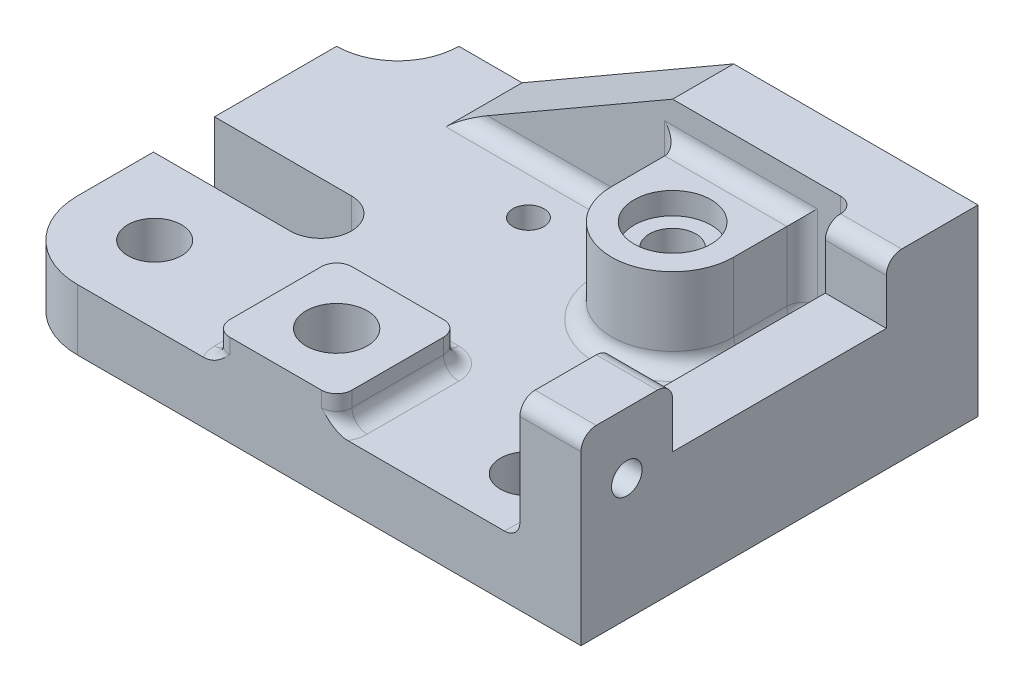
SolidWorks part; units mm, degrees
ref_plane "Front Plane" through (0, 0, 0) normal (0, 0, 1) x (1, 0, 0)
ref_plane "Top Plane" through (0, 0, 0) normal (0, 1, 0) x (1, 0, 0)
ref_plane "Right Plane" through (0, 0, 0) normal (1, 0, 0) x (0, 0, -1)
sketch "Sketch1" plane through (0, 0, 0) normal (0, 1, 0) x (1, 0, 0)
  line L1 (-60.325, 41.275) -> (60.325, 41.275)
  line L2 (-60.325, 41.275) -> (-60.325, -41.275)
  line L3 (-60.325, -41.275) -> (60.325, -41.275)
  line L4 (60.325, 41.275) -> (60.325, -41.275)
  line L5 (-60.325, 41.275) -> (60.325, -41.275) construction
  line L6 (-60.325, -41.275) -> (60.325, 41.275) construction
  point P0 (0, 0)
  dimension "D1" = 82.55
  dimension "D2" = 120.65
extrude "Boss-Extrude1" add sketch "Sketch1" along normal blind 12.7
ref_plane "Plane1" through (0, 12.7, 0) normal (0, 1, 0) x (1, 0, 0)
sketch "Sketch2" plane through (0, 12.7, 0) normal (0, 1, 0) x (1, 0, 0)
  line L0 (60.325, 41.275) -> (-60.325, 41.275) construction
  line L1 (-60.325, 41.275) -> (-60.325, -41.275) construction
  line L2 (-47.625, 41.275) -> (-60.325, 41.275)
  line L3 (-60.325, 41.275) -> (-60.325, 28.575)
  line L4 (-60.325, 3.175) -> (-31.877, 3.175)
  line L6 (-31.877, -9.525) -> (-60.325, -9.525)
  line L7 (-60.325, -9.525) -> (-60.325, 3.175)
  line L8 (9.525, 41.275) -> (9.525, 28.575)
  line L9 (9.525, 28.575) -> (47.625, 28.575)
  line L10 (47.625, 28.575) -> (47.625, -41.275)
  line L11 (-60.325, -41.275) -> (60.325, -41.275) construction
  line L12 (47.625, -41.275) -> (60.325, -41.275)
  line L13 (60.325, -41.275) -> (60.325, 41.275)
  line L14 (60.325, 41.275) -> (9.525, 41.275)
  line L18 (36.449, 28.575) -> (11.049, 28.575)
  line L19 (36.449, 28.575) -> (11.049, 28.575)
  line L20 (-15.875, -41.275) -> (-15.875, -15.875)
  line L21 (-15.875, -15.875) -> (9.525, -15.875)
  line L22 (9.525, -15.875) -> (9.525, -41.275)
  line L23 (9.525, -41.275) -> (-15.875, -41.275)
  line L24 (36.449, -9.525) -> (36.449, -28.575) construction
  line L25 (36.449, -28.575) -> (36.449, -41.275) construction
  line L26 (11.049, 28.575) -> (11.049, 14.351)
  line L28 (36.449, 14.351) -> (36.449, 28.575)
  line L29 (36.449, 28.575) -> (11.049, 28.575)
  line L30 (23.749, 28.575) -> (23.749, 1.651) construction
  line L31 (11.049, 14.351) -> (36.449, 14.351) construction
  arc A0 (-47.625, 41.275) -> (-60.325, 28.575) centre (-60.325, 41.275) cw
  arc A1 (-31.877, 3.175) -> (-31.877, -9.525) centre (-31.877, -3.175) cw
  circle A3 centre (36.449, -9.525) radius 5.588
  circle A4 centre (36.449, -28.575) radius 5.588
  circle A5 centre (-9.525, 17.653) radius 3.2312
  circle A6 centre (-44.323, -25.273) radius 5.588
  circle A7 centre (-3.175, -28.575) radius 6.35
  arc A8 (11.049, 14.351) -> (36.449, 14.351) centre (23.749, 14.351) ccw
  dimension "D1" = 12.7
  dimension "D3" = 6.35
  dimension "D7" = 11.176
  dimension "D8" = 11.176
  dimension "D9" = 11.176
  dimension "D14" = 14.224
  dimension "D26" = 12.7
  dimension "D13" = 12.7
  dimension "D2" = 28.448
  dimension "D4" = 38.1
  dimension "D5" = 16.002
  dimension "D6" = 16.002
  dimension "D10" = 19.05
  dimension "D11" = 12.7
  dimension "D12" = 11.176
  dimension "D15" = 12.7
  dimension "D16" = 12.7
  dimension "D17" = 12.7
  dimension "D18" = 50.8
  dimension "D19" = 23.622
  dimension "D20" = 50.8
  dimension "D21" = 50.8
  dimension "D22" = 25.4
  dimension "D23" = 25.4
  dimension "D24" = 12.7
  dimension "D25" = 12.7
fillet "Fillet1" radius 16.002 1 edges at (-60.325, 6.35, 41.275)
extrude "Cut-Extrude1" cut sketch "Sketch2" against normal blind 12.7 contours A1 L6 L7 L4 | A0 L3 L2 | A5 | A6 | A3 | A4 | A7
extrude "Boss-Extrude2" add sketch "Sketch2<5>" along normal blind 6.35 contours L22 L23 L20 L21 | A7
sketch "Sketch2<5>" plane through (0, 12.7, 0) normal (0, 1, 0) x (1, 0, 0) same geometry as "Sketch2"
extrude "Boss-Extrude3" add sketch "Sketch2<6>" along normal blind 25.4 contours L13 L14 L8 L9 L10 L12 region at (34.925, 12.7, -40.3057)
sketch "Sketch2<6>" plane through (0, 12.7, 0) normal (0, 1, 0) x (1, 0, 0) same geometry as "Sketch2"
extrude "Boss-Extrude4" add sketch "Sketch2<10>" along normal blind 17.526 contours L26 A8 L28 L29
sketch "Sketch2<10>" plane through (0, 12.7, 0) normal (0, 1, 0) x (1, 0, 0) same geometry as "Sketch2"
ref_plane "Plane4" through (0, 0, -41.275) normal (0, 0, -1) x (-1, 0, 0)
sketch "Sketch4" plane through (0, 0, -41.275) normal (0, 0, -1) x (-1, 0, 0)
  line L0 (-9.525, 38.1) -> (-9.525, 12.7)
  line L1 (-9.525, 12.7) -> (34.4691, 12.7)
  line L2 (-9.525, 12.7) -> (47.625, 12.7) construction
  line L3 (34.4691, 12.7) -> (-9.525, 38.1)
  dimension "D1" = 30
extrude "Boss-Extrude5" add sketch "Sketch4" against normal blind 12.7
fillet "Fillet2" radius 3.175 10 edges at (36.449, 12.7, -21.463) (23.749, 12.7, -1.651) (47.625, 25.4, -28.575) (36.449, 21.463, -28.575) (23.749, 30.226, -28.575) (11.049, 21.463, -28.575) (47.625, 12.7, 6.35) (42.037, 12.7, -28.575) (11.049, 12.7, -21.463) (-11.71, 12.7, -28.575)
fillet "Fillet3" radius 3.175 4 edges at (9.525, 15.875, 41.275) (9.525, 15.875, 15.875) (-15.875, 15.875, 15.875) (-15.875, 15.875, 41.275)
fillet "Fillet4" radius 3.175 7 edges at (-14.9451, 12.7, 40.3451) (8.5951, 12.7, 40.3451) (9.525, 12.7, 28.575) (8.5951, 12.7, 16.8049) (-3.175, 12.7, 15.875) (-14.9451, 12.7, 16.8049) (-15.875, 12.7, 28.575)
ref_plane "Plane5" through (0, 30.226, 0) normal (0, 1, 0) x (1, 0, 0)
sketch "Sketch5" plane through (0, 30.226, 0) normal (0, 1, 0) x (1, 0, 0)
  line L0 (23.749, 1.651) -> (23.749, 28.575) construction
  line L1 (7.874, 28.575) -> (39.624, 28.575) construction
  arc A0 (11.049, 14.351) -> (36.449, 14.351) centre (23.749, 14.351) ccw construction
  circle A2 centre (23.749, 14.351) radius 8.001
  point P9 (0, 0)
  dimension "D2" = 16.002
  dimension "D1" = 14.224
extrude "Cut-Extrude2" cut sketch "Sketch5" against normal blind 4.572 contours A2
ref_plane "Plane6" through (0, 25.654, 0) normal (0, 1, 0) x (1, 0, 0)
sketch "Sketch6" plane through (0, 25.654, 0) normal (0, 1, 0) x (1, 0, 0)
  circle A0 centre (23.749, 14.351) radius 4.826
  dimension "D1" = 9.652
extrude "Cut-Extrude3" cut sketch "Sketch6" against normal blind 25.654
ref_plane "Plane7" through (60.325, 0, 0) normal (1, 0, 0) x (0, 0, -1)
sketch "Sketch7" plane through (60.325, 0, 0) normal (1, 0, 0) x (0, 0, -1)
  line L0 (-22.225, 38.1) -> (-22.225, 25.4)
  line L1 (-41.275, 38.1) -> (41.275, 38.1) construction
  line L2 (-22.225, 25.4) -> (22.225, 25.4)
  line L3 (22.225, 25.4) -> (22.225, 38.1)
  line L4 (22.225, 38.1) -> (-22.225, 38.1)
  line L5 (-41.275, 38.1) -> (-41.275, 0) construction
  line L6 (41.275, 38.1) -> (41.275, 0) construction
  dimension "D1" = 12.7
  dimension "D2" = 19.05
  dimension "D3" = 19.05
extrude "Cut-Extrude4" cut sketch "Sketch7" against normal blind 12.7
fillet "Fillet5" radius 3.175 1 edges at (53.975, 38.1, -22.225)
fillet "Fillet6" radius 3.175 2 edges at (53.975, 38.1, 41.275) (53.975, 38.1, 22.225)
sketch "Sketch8" plane through (60.325, 0, 0) normal (1, 0, 0) x (0, 0, -1)
  line L1 (-31.75, 38.1) -> (-31.75, 0) construction
  line L2 (-38.1, 38.1) -> (-25.4, 38.1) construction
  line L3 (-41.275, 0) -> (41.275, 0) construction
  circle A0 centre (-31.75, 25.4) radius 3.175
  point P8 (0, 0)
  point P9 (0, 0)
  dimension "D2" = 6.35
  dimension "D1" = 25.4
extrude "Cut-Extrude5" cut sketch "Sketch8" against normal blind 12.7
